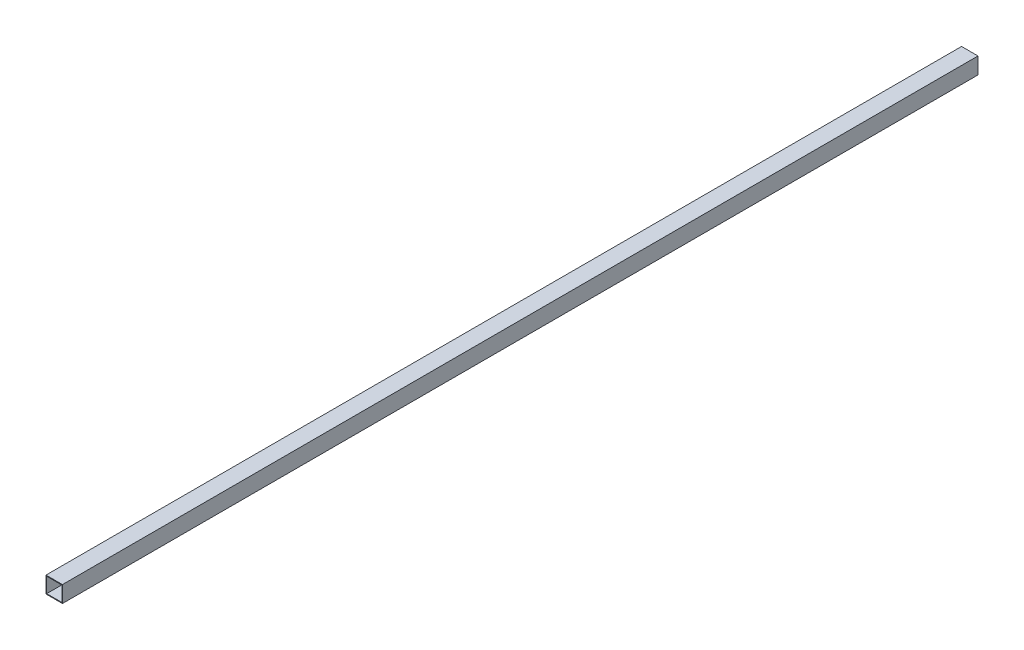
SolidWorks part; units mm, degrees
material "6061-T6 (SS)"
ref_plane "Front Plane" through (0, 0, 0) normal (0, 0, 1) x (1, 0, 0)
ref_plane "Top Plane" through (0, 0, 0) normal (0, 1, 0) x (1, 0, 0)
ref_plane "Right Plane" through (0, 0, 0) normal (1, 0, 0) x (0, 0, -1)
sketch "Sketch2" plane through (0, 0, 0) normal (0, 0, 1) x (1, 0, 0)
  line L0 (0, 19.05) -> (1.5875, 19.05) construction
  line L1 (0, 0) -> (38.1, 0)
  line L2 (0, 0) -> (0, 38.1)
  line L3 (0, 38.1) -> (38.1, 38.1)
  line L4 (38.1, 0) -> (38.1, 38.1)
  line L5 (1.5875, 1.5875) -> (36.5125, 1.5875)
  line L6 (1.5875, 1.5875) -> (1.5875, 36.5125)
  line L7 (1.5875, 36.5125) -> (36.5125, 36.5125)
  line L8 (36.5125, 1.5875) -> (36.5125, 36.5125)
  line L9 (19.05, 36.5125) -> (19.05, 38.1) construction
  line L10 (36.5125, 19.05) -> (38.1, 19.05) construction
  line L11 (19.05, 0) -> (19.05, 1.5875) construction
  dimension "D1" = 38.1
  dimension "D2" = 1.5875
  dimension "D3" = 38.1
extrude "Boss-Extrude1" add sketch "Sketch2" along normal blind 2120.9
